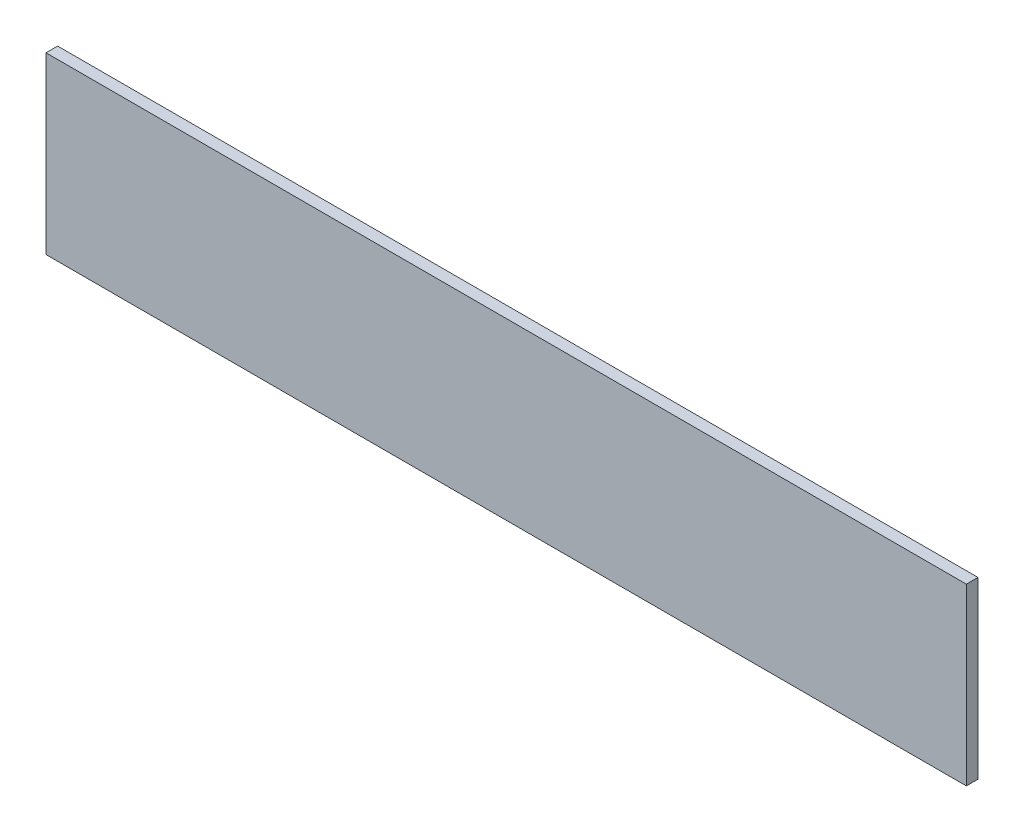
SolidWorks part; units mm, degrees
ref_plane "Ebene vorne" through (0, 0, 0) normal (0, 0, 1) x (1, 0, 0)
ref_plane "Ebene oben" through (0, 0, 0) normal (0, 1, 0) x (1, 0, 0)
ref_plane "Ebene rechts" through (0, 0, 0) normal (1, 0, 0) x (0, 0, -1)
sketch "Skizze1" plane through (0, 0, 0) normal (0, 0, 1) x (1, 0, 0)
  line L1 (395, 75) -> (-395, 75)
  line L2 (395, 75) -> (395, -75)
  line L3 (395, -75) -> (-395, -75)
  line L4 (-395, 75) -> (-395, -75)
  line L5 (395, 75) -> (-395, -75) construction
  line L6 (395, -75) -> (-395, 75) construction
  point P0 (0, 0)
  dimension "D1" = 150
  dimension "D2" = 790
extrude "Aufsatz-Linear austragen1" add sketch "Skizze1" along normal blind 10
